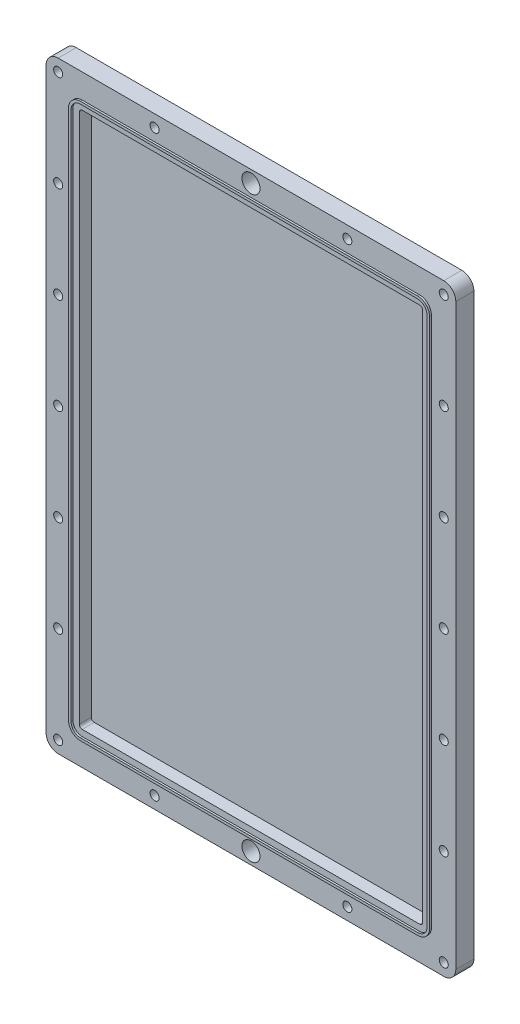
SolidWorks part; units mm, degrees
ref_plane "Front Plane" through (0, 0, 0) normal (0, 0, 1) x (1, 0, 0)
ref_plane "Top Plane" through (0, 0, 0) normal (0, 1, 0) x (1, 0, 0)
ref_plane "Right Plane" through (0, 0, 0) normal (1, 0, 0) x (0, 0, -1)
sketch "Sketch1" plane through (0, 0, 0) normal (0, 0, 1) x (1, 0, 0)
  line L1 (0, 0) -> (215.9, 0)
  line L2 (0, 0) -> (0, 317.5)
  line L3 (0, 317.5) -> (215.9, 317.5)
  line L4 (215.9, 0) -> (215.9, 317.5)
  dimension "D1" = 317.5
  dimension "D2" = 215.9
extrude "Boss-Extrude1" add sketch "Sketch1" along normal blind 9.525
sketch "Sketch4" plane through (0, 0, 9.525) normal (0, 0, 1) x (1, 0, 0)
  line L3 (0, 317.5) -> (0, 0) construction
  line L4 (6.35, 311.15) -> (209.55, 311.15) construction
  line L5 (6.35, 311.15) -> (6.35, 6.35) construction
  line L6 (6.35, 6.35) -> (209.55, 6.35) construction
  line L7 (209.55, 311.15) -> (209.55, 6.35) construction
  line L8 (215.9, 317.5) -> (0, 317.5) construction
  line L9 (215.9, 0) -> (215.9, 317.5) construction
  line L10 (0, 0) -> (215.9, 0) construction
  circle A0 centre (6.35, 6.35) radius 2.3813
  circle A1 centre (6.35, 311.15) radius 2.3813
  circle A2 centre (209.55, 311.15) radius 2.3813
  circle A3 centre (209.55, 6.35) radius 2.3813
  circle A4 centre (57.15, 311.15) radius 2.3813
  circle A5 centre (57.15, 6.35) radius 2.3812
  circle A6 centre (107.95, 311.15) radius 2.3813
  circle A7 centre (107.95, 6.35) radius 2.3813
  circle A8 centre (158.75, 311.15) radius 2.3813
  circle A9 centre (158.75, 6.35) radius 2.3813
  circle A10 centre (6.35, 260.35) radius 2.3813
  circle A11 centre (209.55, 260.35) radius 2.3813
  circle A12 centre (6.35, 209.55) radius 2.3813
  circle A13 centre (209.55, 209.55) radius 2.3813
  circle A14 centre (6.35, 158.75) radius 2.3812
  circle A15 centre (209.55, 158.75) radius 2.3813
  circle A16 centre (6.35, 107.95) radius 2.3812
  circle A17 centre (209.55, 107.95) radius 2.3813
  circle A18 centre (6.35, 57.15) radius 2.3813
  circle A19 centre (209.55, 57.15) radius 2.3813
  dimension "D5" = 4.7625
  dimension "D1" = 6.35
  dimension "D2" = 6.35
  dimension "D3" = 6.35
  dimension "D4" = 6.35
  dimension "D6" = 4
  dimension "D7" = 6
extrude "Cut-Extrude1" cut sketch "Sketch4" against normal through all
sketch "Sketch5" plane through (0, 0, 9.525) normal (0, 0, 1) x (1, 0, 0)
  line L0 (0, 317.5) -> (0, 0) construction
  line L1 (19.05, 304.8) -> (196.85, 304.8) construction
  line L2 (12.7, 298.45) -> (12.7, 19.05) construction
  line L3 (19.05, 12.7) -> (196.85, 12.7) construction
  line L4 (203.2, 298.45) -> (203.2, 19.05) construction
  line L5 (215.9, 317.5) -> (0, 317.5) construction
  line L6 (215.9, 0) -> (215.9, 317.5) construction
  line L7 (0, 0) -> (215.9, 0) construction
  line L8 (19.05, 14.2875) -> (196.85, 14.2875) construction
  line L9 (14.2875, 298.45) -> (14.2875, 19.05) construction
  line L10 (19.05, 303.2125) -> (196.85, 303.2125) construction
  line L11 (201.6125, 298.45) -> (201.6125, 19.05) construction
  line L12 (12.827, 298.45) -> (12.827, 19.05)
  line L13 (19.05, 304.673) -> (196.85, 304.673)
  line L14 (203.073, 298.45) -> (203.073, 19.05)
  line L15 (19.05, 12.827) -> (196.85, 12.827)
  line L16 (201.7395, 298.45) -> (201.7395, 19.05)
  line L17 (19.05, 303.3395) -> (196.85, 303.3395)
  line L18 (14.1605, 298.45) -> (14.1605, 19.05)
  line L19 (19.05, 14.1605) -> (196.85, 14.1605)
  arc A0 (196.85, 12.7) -> (203.2, 19.05) centre (196.85, 19.05) ccw construction
  arc A1 (12.7, 19.05) -> (19.05, 12.7) centre (19.05, 19.05) ccw construction
  arc A2 (196.85, 304.8) -> (203.2, 298.45) centre (196.85, 298.45) cw construction
  arc A3 (19.05, 304.8) -> (12.7, 298.45) centre (19.05, 298.45) ccw construction
  arc A4 (14.2875, 19.05) -> (19.05, 14.2875) centre (19.05, 19.05) ccw construction
  arc A5 (19.05, 303.2125) -> (14.2875, 298.45) centre (19.05, 298.45) ccw construction
  arc A6 (196.85, 303.2125) -> (201.6125, 298.45) centre (196.85, 298.45) cw construction
  arc A7 (196.85, 14.2875) -> (201.6125, 19.05) centre (196.85, 19.05) ccw construction
  arc A8 (19.05, 304.673) -> (12.827, 298.45) centre (19.05, 298.45) ccw
  arc A9 (196.85, 304.673) -> (203.073, 298.45) centre (196.85, 298.45) cw
  arc A10 (196.85, 12.827) -> (203.073, 19.05) centre (196.85, 19.05) ccw
  arc A11 (12.827, 19.05) -> (19.05, 12.827) centre (19.05, 19.05) ccw
  arc A12 (196.85, 303.3395) -> (201.7395, 298.45) centre (196.85, 298.45) cw
  arc A13 (19.05, 303.3395) -> (14.1605, 298.45) centre (19.05, 298.45) ccw
  arc A14 (14.1605, 19.05) -> (19.05, 14.1605) centre (19.05, 19.05) ccw
  arc A15 (196.85, 14.1605) -> (201.7395, 19.05) centre (196.85, 19.05) ccw
  dimension "D5" = 6.35
  dimension "D1" = 12.7
  dimension "D2" = 12.7
  dimension "D3" = 12.7
  dimension "D4" = 12.7
  dimension "D6" = 1.5875
  dimension "D7" = 1.5875
  dimension "D8" = 0.127
  dimension "D9" = 0.127
  dimension "D10" = 0.127
sketch "Sketch6" plane through (0, 0, 9.525) normal (0, 0, 1) x (1, 0, 0)
  line L24 (196.85, 300.0375) -> (19.05, 300.0375)
  line L25 (198.4375, 19.05) -> (198.4375, 298.45)
  line L26 (19.05, 17.4625) -> (196.85, 17.4625)
  line L27 (17.4625, 298.45) -> (17.4625, 19.05)
  line L28 (196.85, 300.0375) -> (19.05, 300.0375)
  line L29 (198.4375, 19.05) -> (198.4375, 298.45)
  line L30 (19.05, 17.4625) -> (196.85, 17.4625)
  line L31 (17.4625, 298.45) -> (17.4625, 19.05)
  arc A20 (19.05, 300.0375) -> (17.4625, 298.45) centre (19.05, 298.45) ccw
  arc A21 (198.4375, 298.45) -> (196.85, 300.0375) centre (196.85, 298.45) ccw
  arc A22 (196.85, 17.4625) -> (198.4375, 19.05) centre (196.85, 19.05) ccw
  arc A23 (17.4625, 19.05) -> (19.05, 17.4625) centre (19.05, 19.05) ccw
  arc A24 (19.05, 300.0375) -> (17.4625, 298.45) centre (19.05, 298.45) ccw
  arc A25 (198.4375, 298.45) -> (196.85, 300.0375) centre (196.85, 298.45) ccw
  arc A26 (196.85, 17.4625) -> (198.4375, 19.05) centre (196.85, 19.05) ccw
  arc A27 (17.4625, 19.05) -> (19.05, 17.4625) centre (19.05, 19.05) ccw
  dimension "D1" = 3.175
extrude "Cut-Extrude3" cut sketch "Sketch6" against normal blind 6.35
extrude "Boss-Extrude2" add sketch "Sketch5" along normal blind 1.016 contours L12 A11 L15 A10 L14 A9 L13 A8 A15 L19 A14 L18 A13 L17 A12 L16 region at (14.896, 302.604, 9.525)
sketch "Sketch7" plane through (0, 0, 9.525) normal (0, 0, 1) x (1, 0, 0)
  circle A0 centre (107.95, 6.35) radius 4.7625
  circle A1 centre (107.95, 311.15) radius 4.7625
  dimension "D1" = 9.525
extrude "Cut-Extrude4" cut sketch "Sketch7" against normal through all
fillet "Fillet1" radius 6.35 4 edges at (0, 317.5, 4.7625) (215.9, 317.5, 4.7625) (0, 0, 4.7625) (215.9, 0, 4.7625)
